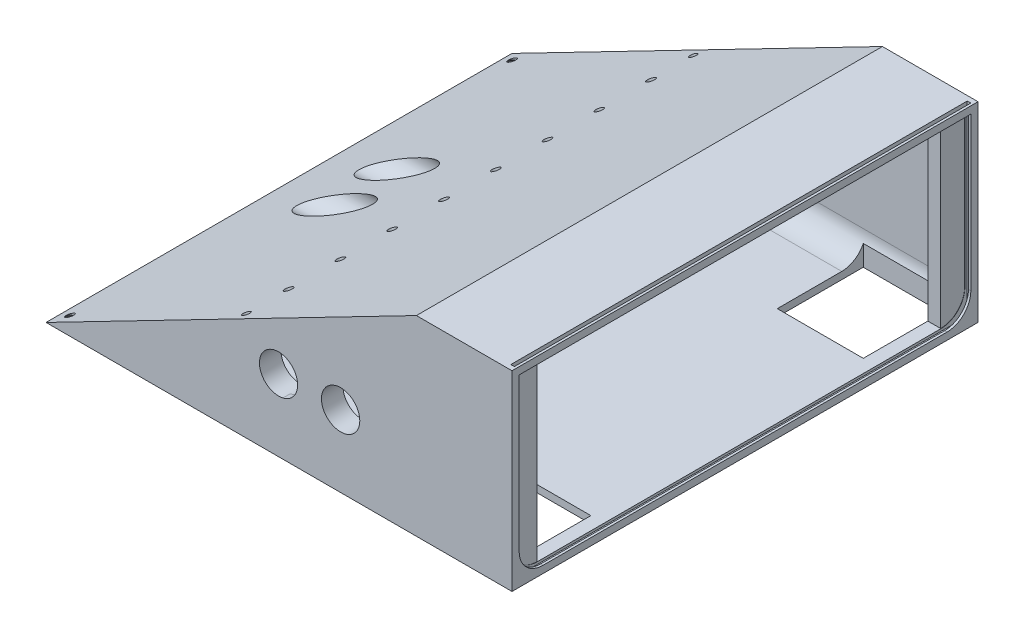
SolidWorks part; units mm, degrees
ref_plane "Front Plane" through (0, 0, 0) normal (0, 0, 1) x (1, 0, 0)
ref_plane "Top Plane" through (0, 0, 0) normal (0, 1, 0) x (1, 0, 0)
ref_plane "Right Plane" through (0, 0, 0) normal (1, 0, 0) x (0, 0, -1)
ref_plane "Plane1" through (0, 0, 0) normal (1, 0, 0) x (0, 0, -1)
ref_plane "Plane2" through (0, 0, 97.5) normal (0, 0, 1) x (1, 0, 0)
ref_plane "Plane3" through (1, 0, 0) normal (1, 0, 0) x (0, 0, -1)
ref_plane "Plane11" through (26, 0, 0) normal (1, 0, 0) x (0, 0, -1)
sketch "Sketch2" plane through (0, 0, 0) normal (0, 0, 1) x (1, 0, 0)
  line L0 (0, 0) -> (195, 0)
  line L1 (195, 0) -> (195, 80)
  line L2 (195, 80) -> (155, 80)
  line L3 (155, 80) -> (0, 0)
  dimension "D1" = 195
  dimension "D2" = 40
  dimension "80" = 80
extrude "Robot" add sketch "Sketch2" along normal blind 195
sketch "Sketch3" plane through (0, 0, 195) normal (0, 0, 1) x (1, 0, 0)
  line L0 (0, 0) -> (195, 0) construction
  circle A0 centre (97.2899, 30) radius 8.02
  circle A1 centre (123.2899, 30) radius 8.02
  dimension "D1" = 30
  dimension "D2" = 16.04
  dimension "D4" = 16.04
  dimension "D3" = 26
  dimension "D5" = 30
sketch "Arriba" plane through (0, 80, 0) normal (0, 1, 0) x (1, 0, 0)
  line L0 (195, 0) -> (195, -195) construction
  line L1 (0, 0) -> (0, -195) construction
  line L2 (0, -97.5) -> (195, -97.5) construction
  line L3 (0, 0) -> (195, 0) construction
  line L4 (0, -195) -> (195, -195) construction
  line L5 (97.5, 0) -> (97.5, -195) construction
sketch "Adelante" plane through (0, 0, 0) normal (1, 0, 0) x (0, 0, -1)
  line L0 (0, 80) -> (0, 0) construction
  line L1 (-97.5, 80) -> (-97.5, 0) construction
  line L2 (0, 80) -> (-195, 80) construction
  line L3 (-195, 0) -> (0, 0) construction
  line L4 (-195, 80) -> (-195, 0) construction
  line L5 (0, 0) -> (-195, 0) construction
sketch "Sketch9" plane through (0, 0, 0) normal (0, 0, -1) x (-1, 0, 0)
  line L1 (0, 0) -> (-195, 0) construction
  circle A0 centre (-97.284, 30) radius 8.2
  circle A1 centre (-123.284, 30) radius 8.2
  dimension "D2" = 16.4
  dimension "D4" = 30
  dimension "D6" = 16.4
  dimension "D3" = 30
  dimension "D5" = 26
sketch "Sketch10" plane through (0, 0, 0) normal (0, -1, 0) x (-1, 0, 0)
  line L0 (0, -195) -> (-195, -195) construction
  line L1 (-187, -191) -> (-150, -191)
  line L2 (-187, -191) -> (-187, -154)
  line L3 (-187, -154) -> (-150, -154)
  line L4 (-150, -191) -> (-150, -154)
  line L5 (-195, 0) -> (-195, -195) construction
  dimension "D1" = 4
  dimension "D2" = 8
  dimension "D3" = 37
  dimension "D4" = 37
sketch "Sketch12" plane through (0, 0, 0) normal (0, -1, 0) x (-1, 0, 0)
  line L0 (-195, 0) -> (-195, -195) construction
  line L1 (-187, -40) -> (-151, -40)
  line L2 (-187, -40) -> (-187, -4)
  line L3 (-187, -4) -> (-151, -4)
  line L4 (-151, -40) -> (-151, -4)
  line L5 (0, 0) -> (-195, 0) construction
  dimension "D1" = 8
  dimension "D2" = 4
  dimension "D3" = 36
  dimension "D4" = 36
sketch "Sketch13" plane through (0, 0, 0) normal (0, -1, 0) x (1, 0, 0)
  line L0 (0, 0) -> (195, 0) construction
  line L1 (26, 8) -> (33.1, 8)
  line L2 (26, 8) -> (26, 15.1)
  line L3 (26, 15.1) -> (33.1, 15.1)
  line L4 (33.1, 8) -> (33.1, 15.1)
  line L5 (0, 0) -> (0, 195) construction
  dimension "D1" = 8
  dimension "D2" = 26
  dimension "D3" = 7.1
  dimension "D4" = 7.1
sketch "Sketch14" plane through (0, 0, 0) normal (0, -1, 0) x (-1, 0, 0)
  line L0 (0, -195) -> (-195, -195) construction
  line L1 (-26, -179.9) -> (-33.1, -179.9)
  line L2 (-26, -179.9) -> (-26, -187)
  line L3 (-26, -187) -> (-33.1, -187)
  line L4 (-33.1, -179.9) -> (-33.1, -187)
  line L5 (0, 0) -> (0, -195) construction
  dimension "D1" = 8
  dimension "D2" = 26
  dimension "D3" = 7.1
  dimension "D4" = 7.1
sketch "Sketch15" plane through (0, 0, 0) normal (0, -1, 0) x (-1, 0, 0)
  line L0 (0, -97.5) -> (-195, -97.5) construction
  line L1 (-26, -93.95) -> (-33.1, -93.95)
  line L2 (-26, -93.95) -> (-26, -101.05)
  line L3 (-26, -101.05) -> (-33.1, -101.05)
  line L4 (-33.1, -93.95) -> (-33.1, -101.05)
  line L5 (0, 0) -> (0, -195) construction
  dimension "D1" = 3.55
  dimension "D2" = 3.55
  dimension "D3" = 7.1
  dimension "D4" = 26
shell "Vacio por dentro 3mm" thickness 3 removed face at (195, 40, 97.5)
extrude "Ultrasonico Derecha" cut sketch "Sketch3" against normal blind 3
sketch "Ultrasonico Centro " plane through (0, 0, 0) normal (1, 0, 0) x (0, 0, -1)
  line L0 (0, 0) -> (-195, 0) construction
  line L1 (-97.5, 80) -> (-97.5, 0) construction
  circle A0 centre (-85, 19) radius 8.7
  circle A1 centre (-111, 19) radius 8.7
  dimension "D2" = 17.4
  dimension "D4" = 17.4
  dimension "D1" = 19
  dimension "D3" = 12.5
  dimension "D5" = 13.5
  dimension "D6" = 19
extrude "Ultrasonico Izquierda" cut sketch "Sketch9" against normal blind 3
extrude "Cut-Extrude4" cut sketch "Ultrasonico Centro " along normal blind 75
sketch "Sketch16" plane through (0, 0, 195) normal (0, 0, 1) x (1, 0, 0)
  circle A0 centre (123.2899, 30) radius 8.02
  circle A1 centre (123.2899, 30) radius 8.6857
  circle A2 centre (97.3351, 30.0107) radius 8.6857
  circle A3 centre (97.3351, 30.0107) radius 8.02
extrude "Boss-Extrude1" add sketch "Sketch16" against normal blind 9
sketch "Sketch18" plane through (1, 0, 0) normal (1, 0, 0) x (0, 0, -1)
  circle A0 centre (-85, 19) radius 8.7
  circle A1 centre (-85, 19) radius 8.2
  circle A2 centre (-111, 19) radius 8.7192
  circle A3 centre (-111, 19) radius 8.2
  dimension "D1" = 17.4
  dimension "D2" = 16.4
  dimension "D3" = 16.4
  dimension "D4" = 17.4384
extrude "Boss-Extrude2" add sketch "Sketch18" along normal blind 60
mirror "Mirror1" about plane through (0, 0, 97.5) normal (0, 0, 1) of "Boss-Extrude1"
extrude "Rueda Derecha" cut sketch "Sketch10" against normal blind 3
extrude "Rueda Izquierda" cut sketch "Sketch12" against normal blind 3
extrude "Cyn70 Derecha" cut sketch "Sketch14" against normal blind 4
extrude "Cny70 Centro" cut sketch "Sketch15" against normal blind 4
extrude "Cny70 Izquierda" cut sketch "Sketch13" against normal blind 4
fillet "Rdondeo" radius 10 2 edges at (103.6768, 3, 3) (103.6768, 3, 192)
ref_plane "Plane4" through (0, 0, 0) normal (-0.4586, 0.8886, 0) x (0.8886, 0.4586, 0)
sketch "Sketch23" plane through (0, 0, 0) normal (-0.4586, 0.8886, 0) x (0.8886, 0.4586, 0)
  line L1 (0, -64.3188) -> (76.5925, -64.3188)
  line L2 (0, -64.3188) -> (0, -130.2867)
  line L3 (0, -130.2867) -> (76.5925, -130.2867)
  line L4 (76.5925, -64.3188) -> (76.5925, -130.2867)
extrude "Cut-Extrude5" cut sketch "Sketch23" along normal blind 25
sketch "Sketch24" plane through (0, 80, 0) normal (0, 1, 0) x (1, 0, 0)
  line L0 (195, 0) -> (155, 0) construction
  line L1 (192.5, -2) -> (194, -2)
  line L2 (192.5, -2) -> (192.5, -193)
  line L3 (192.5, -193) -> (194, -193)
  line L4 (194, -2) -> (194, -193)
  line L5 (195, -195) -> (155, -195) construction
  line L6 (195, -195) -> (195, 0) construction
  dimension "D1" = 2
  dimension "D2" = 2
  dimension "D3" = 1.5
  dimension "D4" = 1
extrude "Cut-Extrude6" cut sketch "Sketch24" against normal blind 78
sketch "Sketch25" plane through (0, 3, 0) normal (0, 1, 0) x (1, 0, 0)
  line L1 (187, -13) -> (192.3997, -13)
  line L2 (187, -13) -> (187, -0.907)
  line L3 (187, -0.907) -> (192.3997, -0.907)
  line L4 (192.3997, -13) -> (192.3997, -0.907)
extrude "Boss-Extrude3" add sketch "Sketch25" along normal blind 75
mirror "Mirror2" about plane through (0, 0, 97.5) normal (0, 0, 1) of "Boss-Extrude3"
ref_plane "Plane5" through (0, 3, 0) normal (0, -1, 0) x (-1, 0, 0)
ref_plane "Plane6" through (0, 0, 0) normal (0, 1, 0) x (1, 0, 0)
ref_plane "Plane10" through (0, 13.25, 0) normal (0, 1, 0) x (1, 0, 0)
ref_plane "Plane13" through (0, 5, 0) normal (0, 1, 0) x (1, 0, 0)
ref_plane "Plane7" through (97.5, 0, 0) normal (1, 0, 0) x (0, 0, -1)
ref_plane "Plane12" through (0, 30, 0) normal (0, 1, 0) x (1, 0, 0)
sketch "Sketch33" plane through (0, 0, 0) normal (0, 1, 0) x (1, 0, 0)
  line L0 (0, -195) -> (195, -195) construction
  line L1 (195, -195) -> (195, 0) construction
  circle A0 centre (190, -190) radius 1.5
  point P0 (190, -190)
  dimension "D1" = 3
  dimension "D2" = 5
  dimension "D3" = 5
hole_wizard "Avellanado para tornillo con cabeza plana de M31" positions "3DSketch5" profile "Sketch37" countersink size "M3" standard "Ansi Metric"
sketch3d "3DSketch5"
  point P0 (190, 0, 190)
sketch "Sketch37" plane through (190, 0, 190) normal (1, 0, 0) x (0, 0, -1)
  line L0 (0, 0) -> (0, 10.9614)
  line L1 (0, 10.9614) -> (1.6, 10)
  line L2 (1.6, 10) -> (1.6, 1.55)
  line L3 (1.6, 1.55) -> (3.15, 0)
  line L5 (3.15, 0) -> (0, 0)
  line L6 (-1.6, 1.55) -> (-3.15, 0) construction
  line L10 (0, 10.9614) -> (-1.6, 10) construction
  line L11 (0, -6.35) -> (0, 107.95) construction
  dimension "Diámetro de taladro" = 3.2
  dimension "Profundidad de taladro" = 10
  dimension "Ángulo de avellanado cercano" = 6.3
  dimension "Ángulo de avellanado lejano" = 90
  dimension "Ángulo de perforador" = 118
mirror "Mirror4" about plane through (0, 0, 97.5) normal (0, 0, 1) of "Avellanado para tornillo con cabeza plana de M31"
mirror "Mirror5" about plane through (97.5, 0, 0) normal (1, 0, 0) of "Mirror4"
sketch "Sketch38" plane through (0, 0, 0) normal (0, 1, 0) x (1, 0, 0)
  line L1 (26.0733, -187.1642) -> (33.1, -187.1642)
  line L2 (26.0733, -187.1642) -> (26.0733, -179.9)
  line L3 (26.0733, -179.9) -> (33.1, -179.9)
  line L4 (33.1, -187.1642) -> (33.1, -179.9)
  line L5 (26.0733, -101.5352) -> (33.1, -101.5352)
  line L6 (26.0733, -101.5352) -> (26.0733, -93.95)
  line L7 (26.0733, -93.95) -> (33.1, -93.95)
  line L8 (33.1, -101.5352) -> (33.1, -93.95)
  line L9 (26.0733, -15.3065) -> (33.1, -15.3065)
  line L10 (26.0733, -15.3065) -> (26.0733, -8)
  line L11 (26.0733, -8) -> (33.1, -8)
  line L12 (33.1, -15.3065) -> (33.1, -8)
  line L13 (25.5733, -7.5) -> (33.6, -7.5)
  line L14 (25.5733, -7.5) -> (25.5733, -15.8065)
  line L15 (25.5733, -15.8065) -> (33.6, -15.8065)
  line L16 (33.6, -7.5) -> (33.6, -15.8065)
  line L17 (25.5733, -93.45) -> (33.6, -93.45)
  line L18 (25.5733, -93.45) -> (25.5733, -102.0352)
  line L19 (25.5733, -102.0352) -> (33.6, -102.0352)
  line L20 (33.6, -93.45) -> (33.6, -102.0352)
  line L21 (25.5733, -179.4) -> (33.6, -179.4)
  line L22 (25.5733, -179.4) -> (25.5733, -187.6642)
  line L23 (25.5733, -187.6642) -> (33.6, -187.6642)
  line L24 (33.6, -179.4) -> (33.6, -187.6642)
  point P16 (25.5733, -11.6532)
  dimension "D1" = 0.5
  dimension "D2" = 0.5
  dimension "D3" = 0.5
  dimension "D4" = 0.5
  dimension "D5" = 0.5
  dimension "D6" = 0.5
  dimension "D7" = 0.5
  dimension "D8" = 0.5
  dimension "D9" = 0.5
  dimension "D10" = 0.5
  dimension "D11" = 0.5
  dimension "D12" = 0.5
extrude "Boss-Extrude4" add sketch "Sketch38" along normal blind 6
sketch "Sketch40" plane through (0, 0, 0) normal (-0.4586, 0.8886, 0) x (0.8886, 0.4586, 0)
  line L1 (174.4276, 0) -> (0, 0) construction
  circle A0 centre (89.8771, -21.6667) radius 1.7
  circle A1 centre (89.8771, -43.3333) radius 1.7
  circle A2 centre (89.8771, -65) radius 1.7
  circle A3 centre (89.8771, -86.6667) radius 1.7
  circle A4 centre (89.8771, -4) radius 1.52
  dimension "D1" = 3.4
  dimension "D3" = 3.4
  dimension "D4" = 21.6667
  dimension "D5" = 3.4
  dimension "D6" = 21.6667
  dimension "D7" = 3.4
  dimension "D8" = 21.6667
  dimension "D9" = 4
  dimension "D10" = 3.04
  dimension "D2" = 21.6667
extrude "Agujeros rampa" cut sketch "Sketch40" against normal blind 3
mirror "Mirror7" about plane through (0, 0, 97.5) normal (0, 0, 1) of "Agujeros rampa"
